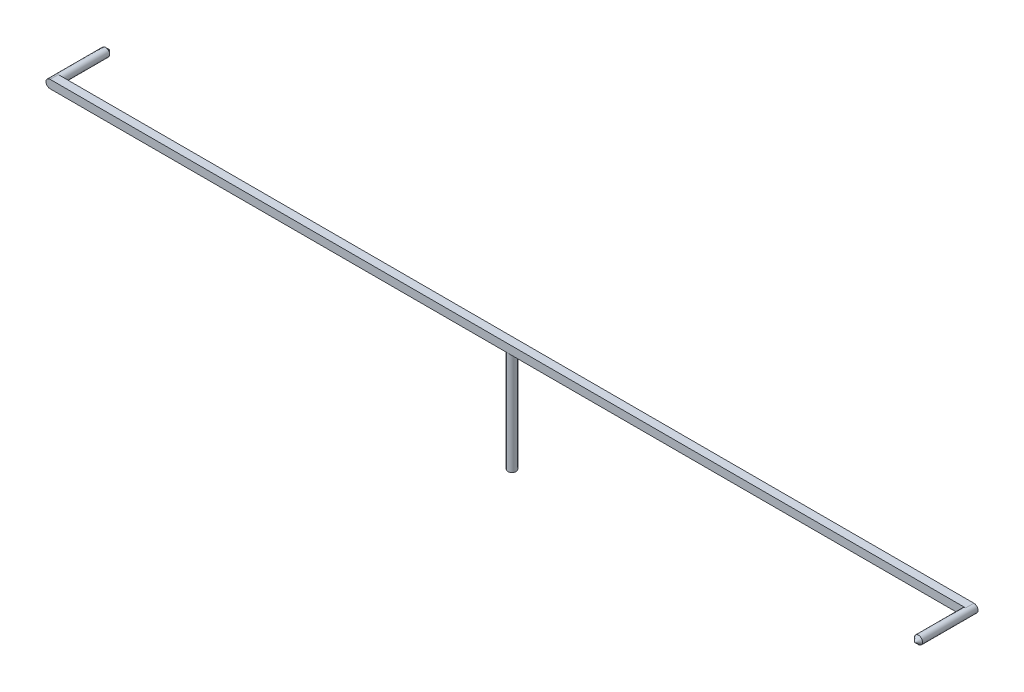
SolidWorks part; units mm, degrees
ref_plane "前视基准面" through (0, 0, 0) normal (0, 0, 1) x (1, 0, 0)
ref_plane "上视基准面" through (0, 0, 0) normal (0, 1, 0) x (1, 0, 0)
ref_plane "右视基准面" through (0, 0, 0) normal (1, 0, 0) x (0, 0, -1)
sketch "草图1" plane through (0, 0, 0) normal (0, 1, 0) x (1, 0, 0)
  circle A0 centre (0, 0) radius 0.4
  dimension "D1" = 0.8
extrude "凸台-拉伸1" add sketch "草图1" along normal blind 10
sketch "草图2" plane through (0, 10, 0) normal (0, 1, 0) x (1, 0, 0)
  line L1 (-45, 0.4) -> (45, 0.4)
  line L2 (-45, 0.4) -> (-45, -0.4)
  line L3 (-45, -0.4) -> (45, -0.4)
  line L4 (45, 0.4) -> (45, -0.4)
  circle A0 centre (0, 0) radius 0.4 construction
  dimension "D1" = 45
  dimension "D2" = 45
extrude "凸台-拉伸2" add sketch "草图2" along normal blind 0.8
fillet "圆角1" radius 0.4 4 edges at (45, 10, 0) (45, 10.8, 0) (-45, 10, 0) (-45, 10.8, 0)
sketch "草图3" plane through (0, 0, 0.4) normal (0, 0, 1) x (1, 0, 0)
  circle A0 centre (44.6, 10.4) radius 0.4
  dimension "D1" = 0.8
extrude "凸台-拉伸3" add sketch "草图3" along normal blind 5
sketch "草图4" plane through (0, 0, -0.4) normal (0, 0, -1) x (-1, 0, 0)
  circle A0 centre (44.6, 10.4) radius 0.4
  dimension "D1" = 0.8
extrude "凸台-拉伸4" add sketch "草图4" along normal blind 5
chamfer "倒角1" distance 0.4 angle 45 2 edges at (-45, 10.4, -5.4) (45, 10.4, 5.4)
